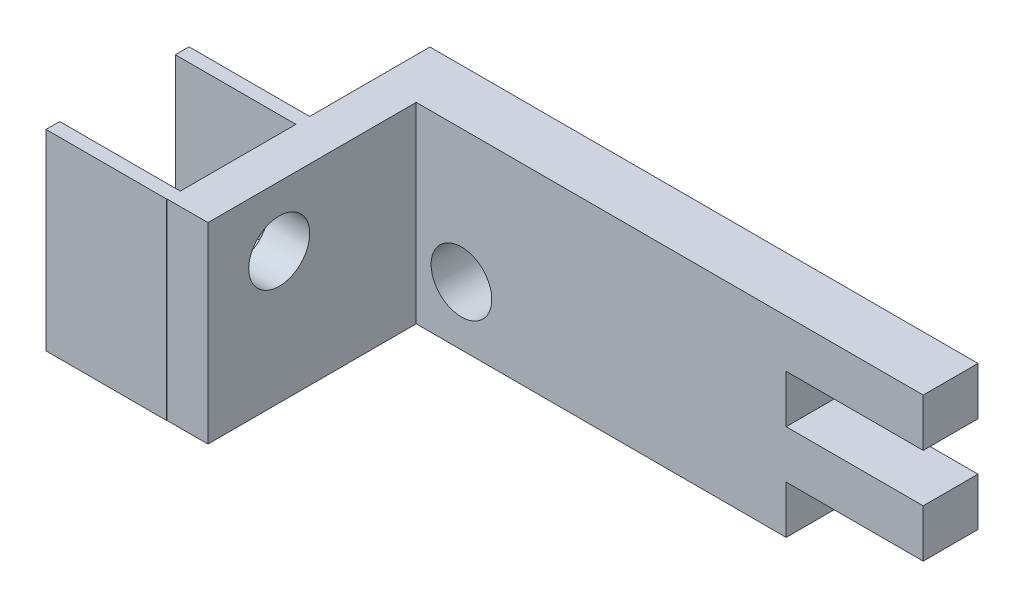
SolidWorks part; units mm, degrees
ref_plane "Alzado" through (0, 0, 0) normal (0, 0, 1) x (1, 0, 0)
ref_plane "Planta" through (0, 0, 0) normal (0, 1, 0) x (1, 0, 0)
ref_plane "Vista lateral" through (0, 0, 0) normal (1, 0, 0) x (0, 0, -1)
sketch "Croquis1" plane through (0, 0, 0) normal (0, 1, 0) x (1, 0, 0)
  line L1 (-175, 45) -> (175, 45)
  line L2 (-175, 45) -> (-175, -45)
  line L3 (-175, -45) -> (175, -45)
  line L4 (175, 45) -> (175, -45)
  line L5 (-175, 45) -> (175, -45) construction
  line L6 (-175, -45) -> (175, 45) construction
  point P0 (0, 0)
  dimension "D1" = 350
  dimension "D2" = 90
extrude "Saliente-Extruir1" add sketch "Croquis1" along normal blind 70
sketch "Croquis2" plane through (0, 70, 0) normal (0, 1, 0) x (1, 0, 0)
  line L0 (-160, -45) -> (-160, 25)
  line L1 (-175, -45) -> (175, -45) construction
  line L2 (-160, 25) -> (160, 25)
  line L3 (160, 25) -> (160, -45)
  line L4 (175, 45) -> (-175, 45) construction
  line L5 (-175, 45) -> (-175, -45) construction
  line L6 (175, -45) -> (175, 45) construction
  line L7 (-160, -45) -> (160, -45)
  dimension "D1" = 20
  dimension "D2" = 15
  dimension "D3" = 15
extrude "Cortar-Extruir1" cut sketch "Croquis2" against normal through all
sketch "Croquis3" plane through (-175, 0, 0) normal (-1, 0, 0) x (0, 0, 1)
  line L0 (25, 26) -> (25, 70) construction
  line L4 (45, 70) -> (-25, 70)
  line L5 (45, 0) -> (45, 70)
  line L6 (-25, 0) -> (45, 0)
  line L7 (-25, 70) -> (-25, 0)
  line L8 (45, 70) -> (-25, 70)
  line L9 (45, 26) -> (45, 70)
  line L11 (-25, 70) -> (-25, 26)
  line L14 (-25, 26) -> (45, 26)
  circle A0 centre (25, 48) radius 11.125
  dimension "D2" = 22.25
  dimension "D3" = 70
  dimension "D4" = 20
  dimension "D5" = 44
  dimension "D1" = 0
extrude "Cortar-Extruir2" cut sketch "Croquis3" against normal through all contours A0
sketch "Croquis8" plane through (0, 0, -45) normal (0, 0, -1) x (-1, 0, 0)
  line L0 (-165, 43) -> (-122, 0) construction
  line L1 (-165, 0) -> (-122, 0)
  line L2 (-165, 0) -> (-165, 43)
  line L3 (-165, 43) -> (-122, 43)
  line L4 (-122, 0) -> (-122, 43)
  line L6 (-175, 0) -> (175, 0) construction
  line L7 (-175, 70) -> (-175, 0) construction
  circle A0 centre (-143.5, 21.5) radius 11.075
  dimension "D3" = 22.15
  dimension "D1" = 43
  dimension "D2" = 43
  dimension "D4" = 10
extrude "Cortar-Extruir3" cut sketch "Croquis8" against normal through all contours A0
mirror "Simetría1" about plane through (0, 0, 0) normal (1, 0, 0) of "Cortar-Extruir3"
thread "Rosca3" pitch 8 method cut profile "Perfil de rosca4" start angle 0, offset 0, length 20, pitch 8, diameter 22.15
ref_plane "Plano4" through (132.425, 21.5, -25) normal (0, -1, 0) x (-1, 0, 0)
sketch "Perfil de rosca4" plane through (132.425, 21.5, -25) normal (0, -1, 0) x (-1, 0, 0)
  line L0 (0, 0) -> (0, 8) construction
  line L1 (0, 0) -> (1.25, 0.3349)
  line L2 (1.25, 0.3349) -> (1.25, 0.933)
  line L3 (1.25, 0.933) -> (0, 1.2679)
  line L4 (1.25, 0.634) -> (0, 0.634) construction
  line L11 (0, 0) -> (0, 1.2679)
  point P2 (0, 0)
  dimension "Pitch" = 8
  dimension "Profile_Angle" = 30
  dimension "Profile_Land" = 0.5981
  dimension "Profile_Height" = 1.25
sketch "Croquis9" plane through (0, 0, -45) normal (0, 0, -1) x (-1, 0, 0)
  line L0 (-25, 17.5) -> (-25, 35)
  line L1 (0, 0) -> (25, 0)
  line L4 (-175, 0) -> (175, 0)
  line L5 (175, 0) -> (175, 70)
  line L6 (175, 70) -> (-175, 70)
  line L7 (-175, 70) -> (-175, 0)
  line L8 (-175, 0) -> (175, 0)
  line L9 (175, 0) -> (175, 70)
  line L10 (175, 70) -> (-175, 70)
  line L11 (-175, 70) -> (-175, 0)
  line L12 (25, 0) -> (25, 17.5)
  line L13 (25, 17.5) -> (-25, 17.5)
  line L14 (-25, 35) -> (25, 35)
  line L15 (25, 35) -> (25, 52.5)
  line L16 (25, 52.5) -> (-25, 52.5)
  line L17 (-25, 52.5) -> (-25, 70)
  dimension "D2" = 17.5
  dimension "D3" = 17.5
  dimension "D4" = 17.5
  dimension "D5" = 25
  dimension "D6" = 50
  dimension "D1" = 0
extrude "Cortar-Extruir6" cut sketch "Croquis9" against normal through all contours L16 L17 L10 L12 L13 L0 L14 L15 region at (85.7143, 33.75, -45)
sketch "Croquis10" plane through (-175, 0, 0) normal (-1, 0, 0) x (0, 0, 1)
  line L0 (51.1, 45.4427) -> (51.1, 70)
  line L1 (51.1, 0) -> (-1.1, 0)
  line L2 (51.1, 0) -> (51.1, 45.4427)
  line L3 (46.1, 26.75) -> (3.9, 26.75)
  line L4 (-1.1, 0) -> (-1.1, 19.9388)
  line L5 (13.875, 48) -> (36.125, 48) construction
  line L6 (51.1, 70) -> (46.1, 70)
  line L7 (-45, 0) -> (45, 0) construction
  line L8 (-1.1, 19.9388) -> (-1.1, 70)
  line L9 (46.1, 70) -> (46.1, 26.75)
  line L11 (-1.1, 70) -> (3.9, 70)
  line L12 (-45, 70) -> (45, 70) construction
  line L13 (3.9, 70) -> (3.9, 26.75)
  circle A0 centre (25, 48) radius 11.125 construction
  point P19 (25, 48)
  point P21 (51.2, 49.4861)
  point P24 (0, 0)
  point P25 (0, 0)
  point P26 (25, 26.75)
  dimension "D1" = 42.2
  dimension "D2" = 21.25
  dimension "D3" = 5
  dimension "D4" = 5
extrude "Saliente-Extruir2" add sketch "Croquis10" along normal blind 44
sketch "Croquis11" plane through (0, 0, 45) normal (0, 0, 1) x (1, 0, 0)
  line L5 (-175, 0) -> (-160, 0)
  line L6 (-160, 0) -> (-160, 70)
  line L7 (-160, 70) -> (-175, 70)
  line L8 (-175, 70) -> (-175, 26.75)
  line L9 (-175, 26.75) -> (-175, 0)
  line L10 (-175, 0) -> (-160, 0)
  line L11 (-160, 0) -> (-160, 70)
  line L12 (-160, 70) -> (-175, 70)
  line L13 (-175, 70) -> (-175, 26.75)
  line L14 (-175, 26.75) -> (-175, 0)
  dimension "D1" = 0
extrude "Saliente-Extruir3" add sketch "Croquis11" along normal blind 6
